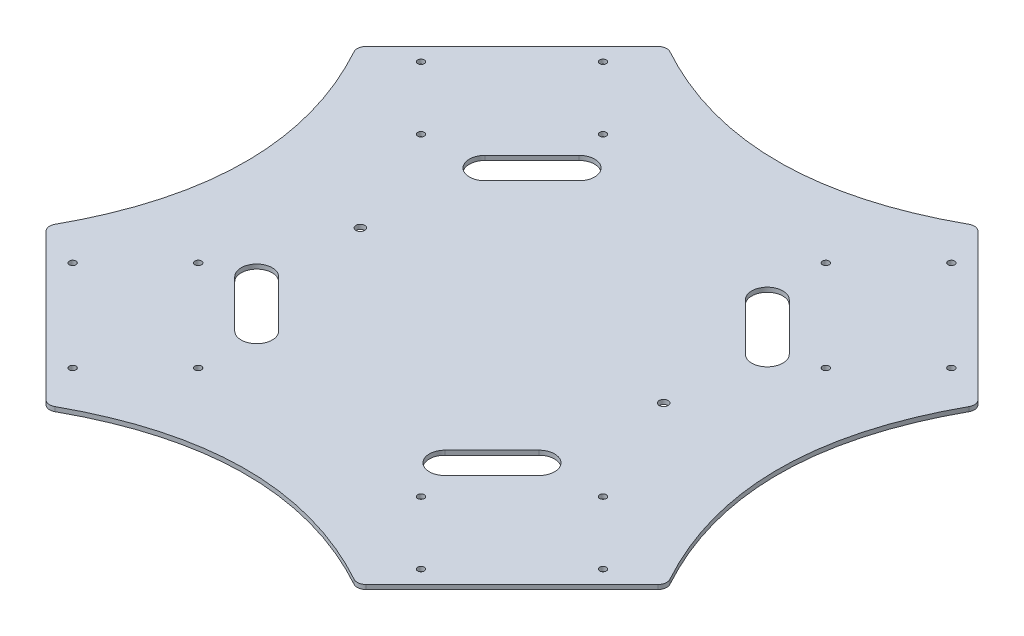
SolidWorks part; units mm, degrees
material "EM-CF"
ref_plane "Płaszczyzna przednia" through (0, 0, 0) normal (0, 0, 1) x (1, 0, 0)
ref_plane "Płaszczyzna górna" through (0, 0, 0) normal (0, 1, 0) x (1, 0, 0)
ref_plane "Płaszczyzna prawa" through (0, 0, 0) normal (1, 0, 0) x (0, 0, -1)
sketch "Szkic1" plane through (0, 0, 0) normal (0, 1, 0) x (1, 0, 0)
  line L0 (0, 0) -> (0, -120) construction
  line L1 (0, -120) -> (0, -140) construction
  line L2 (-70, -140) -> (70, -140) construction
  line L3 (0, 0) -> (-120, 0) construction
  line L4 (-120, 0) -> (-140, 0) construction
  line L5 (-140, 70) -> (-140, -70) construction
  line L6 (0, 0) -> (0, 120) construction
  line L7 (0, 120) -> (0, 140) construction
  line L8 (70, 140) -> (-70, 140) construction
  line L9 (0, 0) -> (120, 0) construction
  line L10 (120, 0) -> (140, 0) construction
  line L11 (140, -70) -> (140, 70) construction
  line L12 (-70, -140) -> (-140, -70)
  line L14 (70, -140) -> (140, -70)
  line L16 (140, 70) -> (70, 140)
  line L17 (-70, 140) -> (-140, 70)
  spline S0 degree 2 poles (-70, -140) (0, -100) (70, -140) knots 0 0 0 1 1 1
  spline S1 degree 2 poles (-140, 70) (-100, 0) (-140, -70) knots 0 0 0 1 1 1
  spline S2 degree 2 poles (70, 140) (0, 100) (-70, 140) knots 0 0 0 1 1 1
  spline S3 degree 2 poles (140, -70) (100, 0) (140, 70) knots 0 0 0 1 1 1
  point P7 (0, -140)
  point P14 (-140, 0)
  point P20 (0, 140)
  point P26 (140, 0)
  point P28 (0, 0)
  dimension "D1" = 120
  dimension "D2" = 20
  dimension "D3" = 140
extrude "Dodanie-wyciągnięcie1" add sketch "Szkic1" along normal blind 2
fillet "Zaokrąglenie1" radius 4 8 edges at (-140, 1, -70) (-70, 1, -140) (70, 1, -140) (140, 1, -70) (140, 1, 70) (70, 1, 140) (-140, 1, 70) (-70, 1, 140)
sketch "Szkic2" plane through (0, 2, 0) normal (0, 1, 0) x (1, 0, 0)
  line L0 (0, 0) -> (-70.7107, -70.7107) construction
  line L1 (-120.2082, -49.4975) -> (-49.4975, -120.2082) construction
  line L2 (-70.7107, -70.7107) -> (-98.9949, -98.9949) construction
  line L3 (-78.4889, -119.501) -> (-119.501, -78.4889) construction
  circle A0 centre (-78.4889, -119.501) radius 1.5
  circle A1 centre (-119.501, -78.4889) radius 1.5
  circle A2 centre (-50.2046, -91.2168) radius 1.5
  circle A3 centre (-91.2168, -50.2046) radius 1.5
  point P6 (-70.7107, -70.7107)
  point P10 (-98.9949, -98.9949)
  point P13 (-84.8528, -84.8528)
  point P16 (-84.8528, -84.8528)
  dimension "D5" = 3
  dimension "D1" = 100
  dimension "D3" = 40
extrude "Wytnij-wyciągnięcie1" cut sketch "Szkic2" against normal through all
ref_axis "Oś1" through (0, -82.2794, 0) along (0, 1, 0)
pattern_circular "Szyk kołowy1" count 4 every 90 about axis through (0, -82.2794, 0) along (0, 1, 0) of "Wytnij-wyciągnięcie1"
sketch "Szkic3" plane through (0, 2, 0) normal (0, 1, 0) x (1, 0, 0)
  line L0 (3.5562, 5.4754) -> (-53.0123, 62.0439) construction
  line L1 (-42.4057, 72.6505) -> (-63.6189, 51.4373)
  line L2 (-63.6189, 51.4373) -> (-42.4057, 72.6505) construction
  line L3 (-68.5687, 56.3871) -> (-47.3554, 77.6003)
  line L4 (-58.6692, 46.4876) -> (-37.456, 67.7008)
  arc A0 (-68.5687, 56.3871) -> (-58.6692, 46.4876) centre (-63.6189, 51.4373) ccw
  arc A1 (-37.456, 67.7008) -> (-47.3554, 77.6003) centre (-42.4057, 72.6505) ccw
  point P2 (-53.0123, 62.0439)
  point P5 (-53.0123, 62.0439)
  dimension "D1" = 80
  dimension "D2" = 30
  dimension "D3" = 14
extrude "Wytnij-wyciągnięcie2" cut sketch "Szkic3" against normal up to next contours L4 A1 L3 A0 region at (-57.6099, 2, -66.6416)
pattern_circular "Szyk kołowy2" count 4 every 90 about axis through (0, -82.2794, 0) along (0, 1, 0) of "Wytnij-wyciągnięcie2"
sketch "Szkic4" plane through (0, 2, 0) normal (0, 1, 0) x (1, 0, 0)
  line L0 (68.34, 0) -> (-68.34, 0) construction
  circle A0 centre (-68.34, 0) radius 2
  circle A1 centre (68.34, 0) radius 2
  point P3 (0, 0)
  dimension "D2" = 4
  dimension "D3" = 4
  dimension "D1" = 136.68
extrude "Wytnij-wyciągnięcie3" cut sketch "Szkic4" against normal up to next
